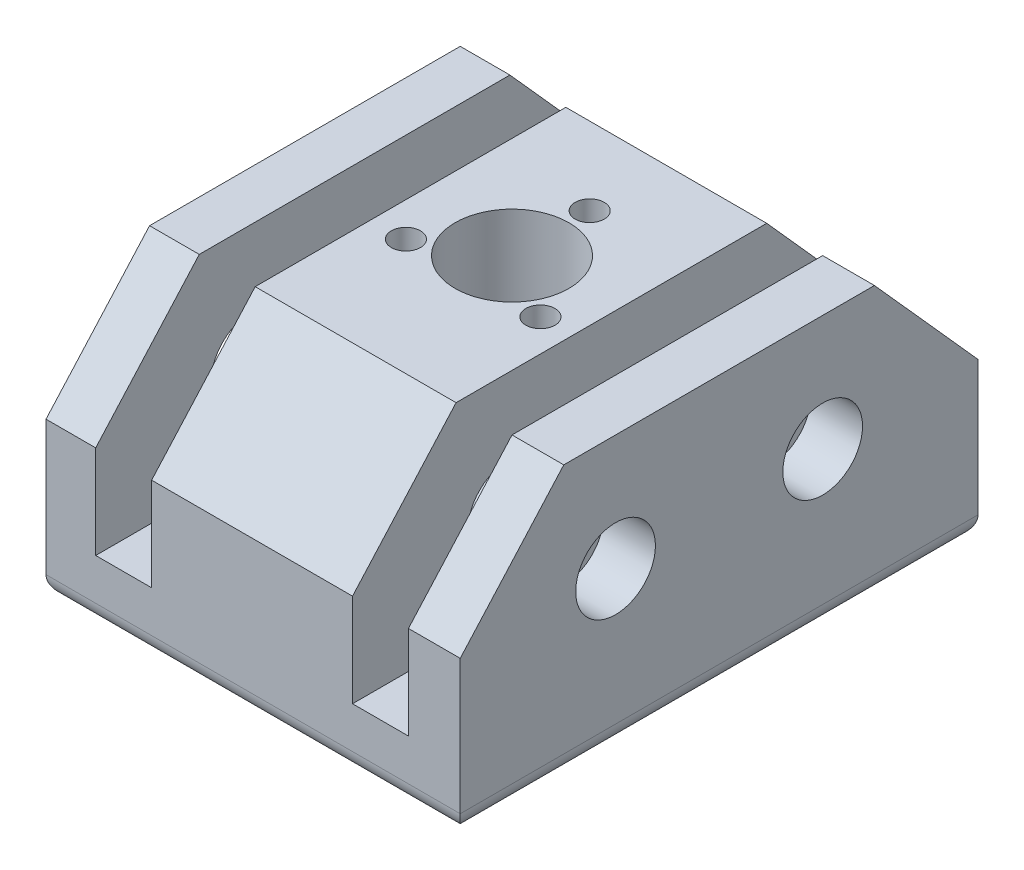
SolidWorks part; units mm, degrees
ref_plane "Front Plane" through (0, 0, 0) normal (0, 0, 1) x (1, 0, 0)
ref_plane "Top Plane" through (0, 0, 0) normal (0, 1, 0) x (1, 0, 0)
ref_plane "Right Plane" through (0, 0, 0) normal (1, 0, 0) x (0, 0, -1)
sketch "Sketch1" plane through (0, 0, 0) normal (1, 0, 0) x (0, 0, -1)
  line L1 (0, 0) -> (63.5, 0)
  line L2 (0, 0) -> (0, 6.35)
  line L3 (0, 6.35) -> (63.5, 6.35)
  line L4 (63.5, 0) -> (63.5, 6.35)
  dimension "D1" = 6.35
  dimension "D2" = 63.5
extrude "Boss-Extrude1" add sketch "Sketch1" against normal blind 50.8
sketch "Sketch2" plane through (0, 0, 0) normal (1, 0, 0) x (0, 0, -1)
  line L0 (0, 6.35) -> (0, 19.05)
  line L1 (0, 19.05) -> (12.7, 33.249)
  line L2 (12.7, 33.249) -> (50.8, 33.249)
  line L3 (50.8, 33.249) -> (63.5, 19.05)
  line L4 (63.5, 19.05) -> (63.5, 6.35)
  line L5 (63.5, 6.35) -> (0, 6.35)
  point P7 (31.75, 33.249)
  point P10 (31.75, 6.35)
  dimension "D1" = 38.1
  dimension "D2" = 12.7
  dimension "D3" = 12.7
  dimension "D4" = 19.05
  dimension "D5" = 19.05
extrude "Boss-Extrude2" add sketch "Sketch2" against normal blind 50.8
sketch "Sketch10" plane through (0, 0, -63.5) normal (0, 0, -1) x (-1, 0, 0)
  line L1 (50.8, 33.249) -> (0, 33.249) construction
  line L3 (6.35, 7.62) -> (6.35, 33.249)
  line L4 (6.35, 33.249) -> (13.208, 33.249)
  line L5 (13.208, 7.62) -> (13.208, 33.249)
  line L6 (6.35, 7.62) -> (13.208, 7.62)
  line L8 (50.8, 0) -> (0, 0) construction
  point P11 (13.208, 7.62)
  dimension "D1" = 7.62
  dimension "D2" = 6.858
  dimension "D3" = 6.35
extrude "Cut-Extrude1" cut sketch "Sketch10" against normal through all
pattern_linear "LPattern3" count 2 spacing 31.496 along (-1, 0, 0) of "Cut-Extrude1"
sketch "Sketch11" plane through (0, 0, 0) normal (1, 0, 0) x (0, 0, -1)
  circle A0 centre (19.05, 19.05) radius 4.8895
  circle A1 centre (19.05, 19.05) radius 7.9375 construction
  circle A2 centre (44.45, 19.05) radius 4.8895
  circle A3 centre (44.45, 19.05) radius 7.9375 construction
  dimension "D1" = 9.779
  dimension "D3" = 15.875
  dimension "D4" = 9.779
  dimension "D6" = 15.875
  dimension "D2" = 6.35
  dimension "D5" = 6.35
extrude "Cut-Extrude2" cut sketch "Sketch11" against normal through all
sketch "Sketch14" plane through (0, 33.249, 0) normal (0, 1, 0) x (1, 0, 0)
  line L3 (-37.846, 12.7) -> (-37.846, 50.8) construction
  point P0 (-25.4, 31.75)
  point P4 (-37.846, 31.75)
  dimension "D1" = 12.446
sketch "Sketch17" plane through (0, 40.0201, -44.7438) normal (0, 0.6667, -0.7454) x (-1, 0, 0)
  line L0 (13.208, -28.1343) -> (13.208, -9.0843) construction
  line L1 (37.846, -9.0843) -> (13.208, -9.0843) construction
  point P0 (25.527, -18.6093)
  point P4 (13.208, -18.6093)
  point P7 (25.527, -9.0843)
sketch "Sketch18" plane through (0, 8.4667, 9.466) normal (0, 0.6667, 0.7454) x (1, 0, 0)
  line L0 (-13.208, 33.249) -> (-13.208, 14.199) construction
  line L1 (-37.846, 33.249) -> (-13.208, 33.249) construction
  point P0 (-25.527, 23.724)
  point P1 (-25.527, 23.724)
  point P4 (-13.208, 23.724)
  point P7 (-25.527, 33.249)
ref_plane "Plane2" through (0, 33.02, 0) normal (0, -1, 0) x (-1, 0, 0)
fillet "Fillet1" radius 2.54 4 edges at (0, 0, -31.75) (-50.8, 0, -31.75) (-25.4, 0, 0) (-25.4, 0, -63.5)
sketch "Sketch24" plane through (0, 0, 0) normal (0, -1, 0) x (1, 0, 0)
  line L0 (-25.4, -63.5) -> (-25.4, 0) construction
  line L1 (-50.8, -63.5) -> (0, -63.5) construction
  line L2 (-50.8, 0) -> (0, 0) construction
  line L3 (0, -31.75) -> (-50.8, -31.75) construction
  line L4 (0, 0) -> (0, -63.5) construction
  line L5 (-50.8, 0) -> (-50.8, -63.5) construction
  circle A0 centre (-25.4, -31.75) radius 6.985
  dimension "D1" = 13.97
extrude "Cut-Extrude10" cut sketch "Sketch24" against normal through all
sketch "Sketch25" plane through (0, 0, 0) normal (0, -1, 0) x (1, 0, 0)
  circle A0 centre (-25.4, -31.75) radius 13.97
  dimension "D1" = 27.94
extrude "Cut-Extrude11" cut sketch "Sketch25" against normal blind 5.08
sketch "Sketch26" plane through (0, 5.08, 0) normal (0, -1, 0) x (1, 0, 0)
  circle A0 centre (-25.4, -31.75) radius 9.525 construction
  circle A1 centre (-25.4, -41.275) radius 1.7859
  circle A2 centre (-33.6489, -26.9875) radius 1.7859
  circle A3 centre (-17.1511, -26.9875) radius 1.7859
  point P11 (-25.4, -31.75)
  dimension "D1" = 3
extrude "Cut-Extrude12" cut sketch "Sketch26" against normal up to next
